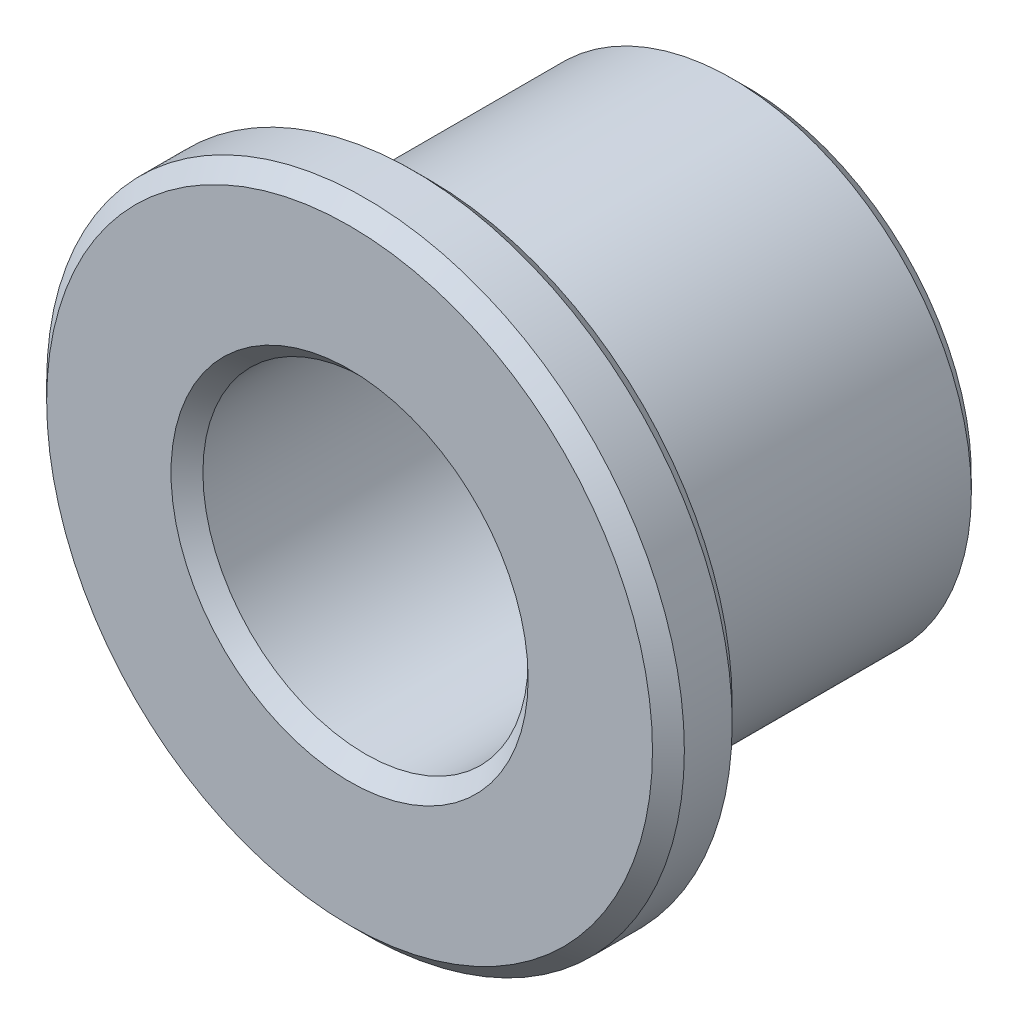
SolidWorks part; units mm, degrees
material "PET"
ref_plane "Front Plane" through (0, 0, 0) normal (0, 0, 1) x (1, 0, 0)
ref_plane "Top Plane" through (0, 0, 0) normal (0, 1, 0) x (1, 0, 0)
ref_plane "Right Plane" through (0, 0, 0) normal (1, 0, 0) x (0, 0, -1)
ref_axis "X AXIS" through (-88.99, 0, 0) along (1, 0, 0)
ref_axis "Y AXIS" through (0, 55, 0) along (0, -1, 0)
ref_axis "Z AXIS" through (0, 0, -88.99) along (0, 0, 1)
sketch "Sketch1" plane through (0, 0, 0) normal (1, 0, 0) x (0, 0, -1)
  line L0 (0, 0) -> (0, 12.7)
  line L1 (0, 55) -> (0, -55) construction
  line L2 (0, 12.7) -> (3.175, 12.7)
  line L3 (3.175, 12.7) -> (3.175, 9.525)
  line L4 (3.175, 9.525) -> (15.875, 9.525)
  line L5 (15.875, 9.525) -> (15.875, 0)
  line L6 (88.99, 0) -> (-88.99, 0) construction
  line L7 (15.875, 0) -> (0, 0)
  line L8 (0, 0) -> (-21.2555, 0) construction
  dimension "D1" = 15.875
  dimension "D2" = 19.05
  dimension "D3" = 3.175
  dimension "D4" = 25.4
revolve "Revolve1" add sketch "Sketch1" angle 360 about L8
sketch "Sketch16" plane through (0, 0, 0) normal (0, 0, 1) x (1, 0, 0)
  circle A0 centre (0, 0) radius 6.477
  dimension "D1" = 12.954
extrude "Cut-Extrude1" cut sketch "Sketch16" against normal up to next
chamfer "Chamfer1" distance 0.635 angle 45 6 edges at (-9.525, 0, -3.175) (-12.7, 0, -3.175) (-6.477, 0, -15.875) (6.477, 0, 0) (-9.525, 0, -15.875) (-12.7, 0, 0)
